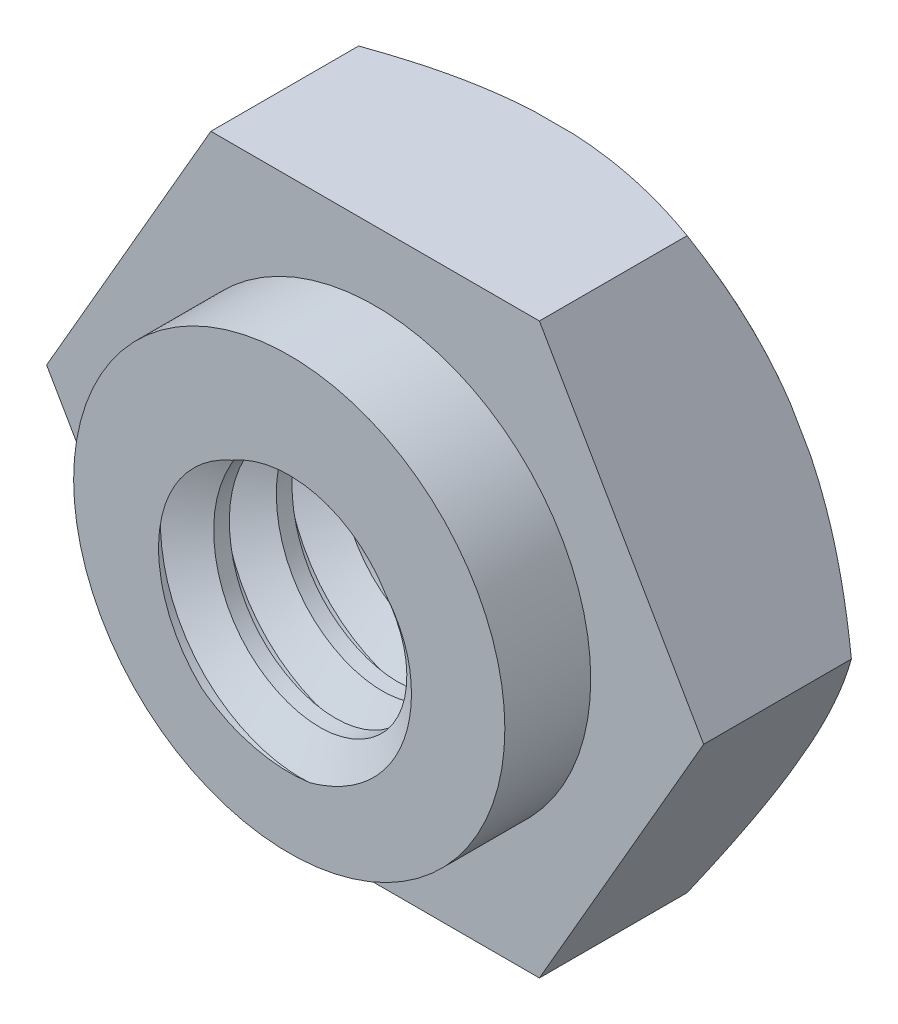
SolidWorks part; units mm, degrees
ref_plane "Front Plane" through (0, 0, 0) normal (0, 0, 1) x (1, 0, 0)
ref_plane "Top Plane" through (0, 0, 0) normal (0, 1, 0) x (1, 0, 0)
ref_plane "Right Plane" through (0, 0, 0) normal (1, 0, 0) x (0, 0, -1)
sketch "Sketch1" plane through (0, 0, 0) normal (0, 0, 1) x (1, 0, 0)
  line L1 (-0.918, -1.59) -> (0.918, -1.59)
  line L2 (0.918, -1.59) -> (1.836, 0)
  line L3 (1.836, 0) -> (0.918, 1.59)
  line L4 (0.918, 1.59) -> (-0.918, 1.59)
  line L5 (-0.918, 1.59) -> (-1.836, 0)
  line L6 (-1.836, 0) -> (-0.918, -1.59)
  circle A0 centre (0, 0) radius 1.59 construction
  dimension "D1" = 3.18
extrude "Boss-Extrude1" add sketch "Sketch1" along normal blind 1
sketch "Sketch2" plane through (0, 0, 1) normal (0, 0, 1) x (1, 0, 0)
  circle A0 centre (0, 0) radius 1.205
  dimension "D1" = 2.41
extrude "Boss-Extrude2" add sketch "Sketch2" along normal blind 0.48
ref_axis "Axis1" through (0, 0, 1.48) along (0, 0, -1)
ref_plane "Plane1" through (0, 0, 0) normal (0, -1, 0) x (-1, 0, 0)
sketch "Sketch3" plane through (0, 0, 0) normal (0, -1, 0) x (-1, 0, 0)
  line L0 (1.5939, 0) -> (1.836, -0.1744)
  line L1 (1.836, 0) -> (0.918, 0) construction
  line L2 (1.836, -1) -> (1.836, 0) construction
  line L3 (1.836, -0.1744) -> (1.836, 0)
  line L4 (1.836, 0) -> (1.5939, 0)
  point P6 (1.836, -0.0907)
  point P9 (1.836, -0.1744)
  point P10 (1.5205, 0)
  point P11 (1.5939, 0)
revolve "Cut-Revolve1" cut sketch "Sketch3" angle 360 about axis through (0, 0, 1.48) along (0, 0, -1)
sketch "Sketch5" plane through (0, 0, 0) normal (0, 0, -1) x (-1, 0, 0)
  point P0 (0, 0)
hole_wizard "M1.6x0.35 Tapped Hole1" positions "Sketch6" profile "Sketch7" tap size "M1.6x0.35" standard "ANSI Metric" end condition through all
sketch "Sketch6" plane through (0, 0, 0) normal (0, 0, -1) x (-1, 0, 0)
  point P1 (0, 0)
sketch "Sketch7" plane through (0, 0, 0) normal (1, 0, 0) x (0, 1, 0)
  line L0 (0, 0) -> (0, 1.48)
  line L1 (0, 1.48) -> (0.625, 1.48)
  line L2 (0.625, 1.48) -> (0.625, 0)
  line L5 (0.625, 0) -> (0, 0)
  line L11 (0, -6.35) -> (0, 107.95) construction
  dimension "Thru Tap Drill Dia." = 1.25
  dimension "Thru Tap Drill Depth" = 1.48
thread "Thread1" pitch 0.35 method cut profile "Thread Profile1" start angle 0, offset 1, length 10, pitch 0.35, diameter 1.25
ref_plane "Plane2" through (0.625, 0, -1) normal (0, -1, 0) x (1, 0, 0)
sketch "Thread Profile1" plane through (0.625, 0, -1) normal (0, -1, 0) x (1, 0, 0)
  line L0 (0, 0) -> (0, 0.35) construction
  line L1 (0, 0) -> (0.1894, 0.1094)
  line L2 (0.1894, 0.1094) -> (0.1894, 0.1531)
  line L3 (0.1894, 0.1531) -> (0, 0.2625)
  line L4 (0.1894, 0.1312) -> (0, 0.1312) construction
  line L11 (0, 0) -> (0, 0.2625)
  point P2 (0, 0)
  dimension "Pitch" = 0.35
  dimension "Profile_Angle" = 60
  dimension "Profile_Land" = 0.0437
  dimension "Profile_Height" = 0.1894
